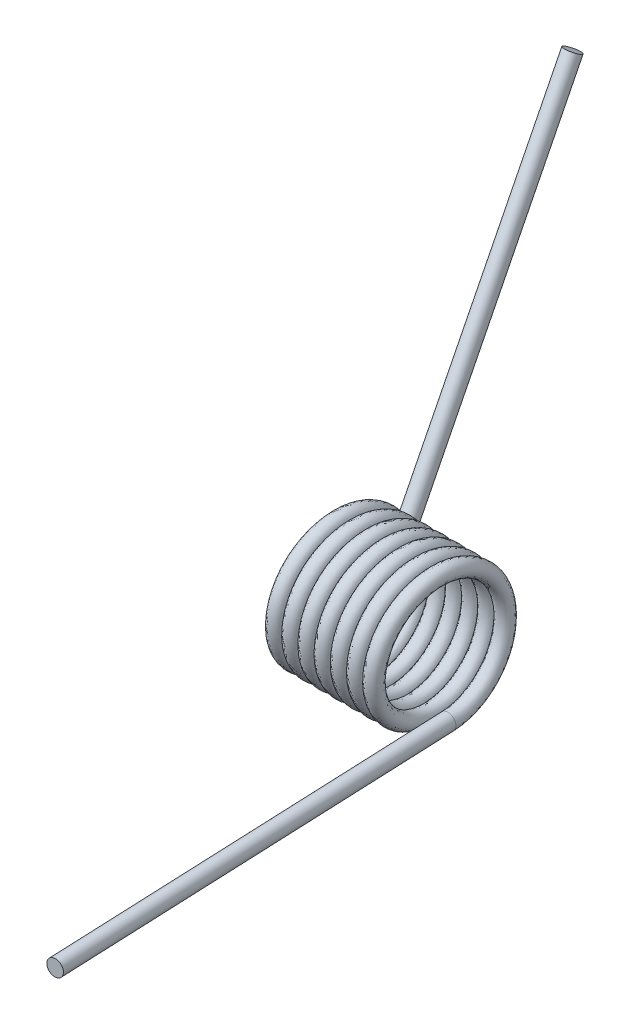
SolidWorks part; units mm, degrees
ref_plane "Front" through (0, 0, 0) normal (0, 0, 1) x (1, 0, 0)
ref_plane "Top" through (0, 0, 0) normal (0, 1, 0) x (1, 0, 0)
ref_plane "Right" through (0, 0, 0) normal (1, 0, 0) x (0, 0, -1)
sketch "Sketch1" plane through (0, 0, 0) normal (1, 0, 0) x (0, 0, -1)
  line L0 (0, 0) -> (0, -6.6294) construction
  line L1 (0, -6.6294) -> (0, -7.62) construction
  line L2 (0, -7.62) -> (0, -8.6106) construction
  line L3 (0, 8.6106) -> (0, -8.6106) construction
  circle A0 centre (0, 0) radius 6.6294 construction
  circle A1 centre (0, 0) radius 8.6106 construction
  circle A2 centre (0, 0) radius 7.62
  circle A3 centre (0, -7.62) radius 0.9906 construction
  circle A4 centre (0, 0) radius 5.1562 construction
curve "Helix/Spiral1" pitch 2.0066 height 14.3806 radius 7.62 left hand yes centre (0, 0, 0) axis (-1, 0, 0) start towards (0, 0, -1)
ref_plane "Plane1" through (0, -7.62, 0) normal (-0.0419, 0, -0.9991) x (0.9988, -0.024, -0.0419)
sketch "Sketch2" plane through (0, -7.62, 0) normal (-0.0419, 0, -0.9991) x (0.9988, -0.024, -0.0419)
  circle A0 centre (0, 0) radius 0.9906
  dimension "D1" = 1.9812
sweep "Sweep1" add profiles "Sketch2" path "Helix/Spiral1"
sketch "Sketch3" plane through (0, 0, 0) normal (0.0419, 0, 0.9991) x (-0.9988, 0.024, 0.0419)
  circle A1 centre (-0.1826, 7.6178) radius 0.9906
  circle A2 centre (-0.1826, 7.6178) radius 0.9906
  dimension "D1" = 0
extrude "Extrude1" add sketch "Sketch3" along normal blind 50.8
sketch "Sketch4" plane through (-0.0252, 0.521, -0.3008) normal (-0.0419, 0.8653, -0.4996) x (0.9991, 0.0363, -0.0209)
  circle A1 centre (-14.368, 7.62) radius 0.9906
  circle A2 centre (-14.368, 7.62) radius 0.9906
  dimension "D1" = 0
extrude "Extrude2" add sketch "Sketch4" along normal blind 50.8
ref_plane "Plane2" through (-0.0252, 0.521, -0.3008) normal (0.0419, -0.8653, 0.4996) x (0.9991, 0.0363, -0.0209)
ref_plane "Plane3" through (0, 0, 0) normal (0.0419, 0, 0.9991) x (0.9991, 0, -0.0419)
ref_axis "Axis1" through (-298.6411, -6.5303, 12.5163) along (0.9988, 0.0242, -0.0419)
equation "\"D4@Helix/Spiral1\"=\"Wire Dia@Sketch1\"+.001"
equation "\"D1@Sketch2\"=\"Wire Dia@Sketch1\""
